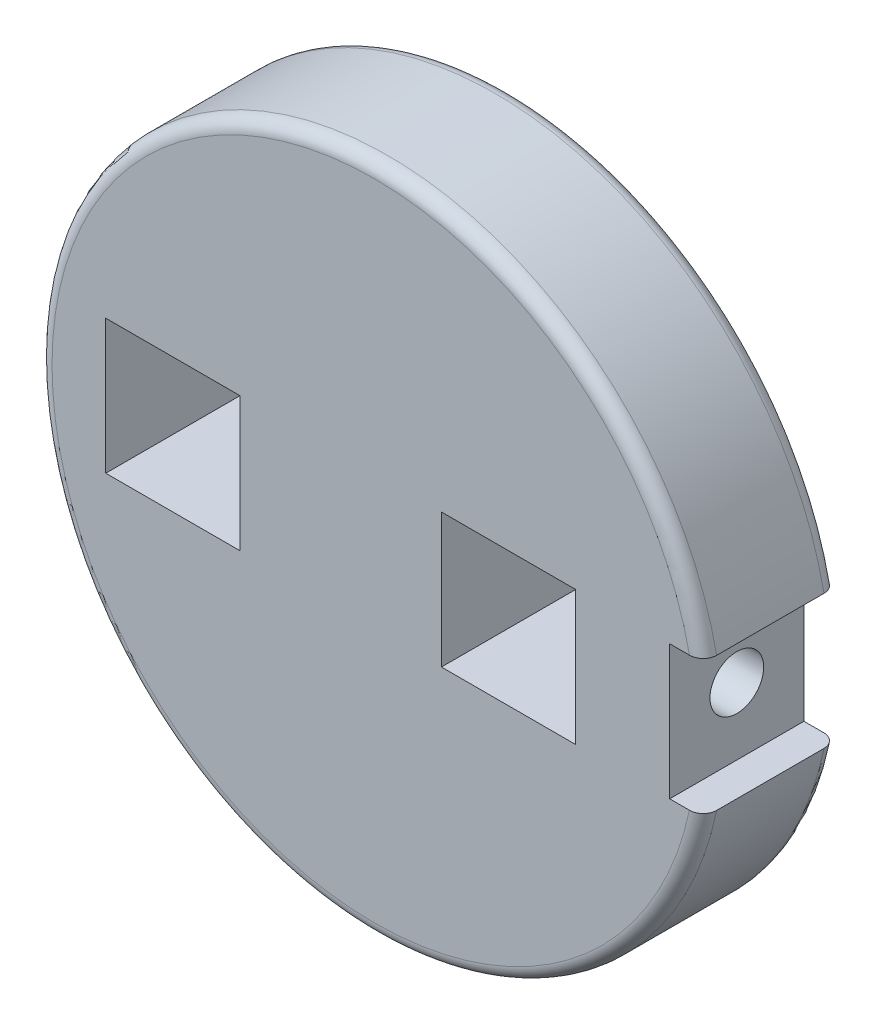
SolidWorks part; units mm, degrees
ref_plane "Front Plane" through (0, 0, 0) normal (0, 0, 1) x (1, 0, 0)
ref_plane "Top Plane" through (0, 0, 0) normal (0, 1, 0) x (1, 0, 0)
ref_plane "Right Plane" through (0, 0, 0) normal (1, 0, 0) x (0, 0, -1)
sketch "Sketch1" plane through (0, 0, 0) normal (0, 0, 1) x (1, 0, 0)
  circle A0 centre (0, 0) radius 25
  dimension "D1" = 50
extrude "Boss-Extrude1" add sketch "Sketch1" along normal blind 10
sketch "Sketch2" plane through (0, 0, 10) normal (0, 0, 1) x (1, 0, 0)
  line L0 (5, -5) -> (15, -5)
  line L1 (-5, -15) -> (5, -15)
  line L2 (-5, -15) -> (-5, -5)
  line L3 (-5, 15) -> (5, 15)
  line L4 (5, -15) -> (5, -5)
  line L5 (-5, -15) -> (5, 15) construction
  line L6 (-5, 15) -> (5, -15) construction
  line L7 (-15, 5) -> (-5, 5)
  line L8 (-15, 5) -> (-15, -5)
  line L9 (-15, -5) -> (-5, -5)
  line L10 (15, 5) -> (15, -5)
  line L11 (-15, 5) -> (15, -5) construction
  line L12 (-15, -5) -> (15, 5) construction
  line L13 (-5, 5) -> (-5, 15)
  line L14 (5, 5) -> (15, 5)
  line L15 (5, 5) -> (5, 15)
  point P0 (0, 0)
  point P5 (0, 0)
  dimension "D1" = 10
  dimension "D2" = 10
  dimension "D3" = 10
  dimension "D4" = 10
extrude "Cut-Extrude1" cut sketch "Sketch2" against normal through all both and the other way through all
sketch "Sketch4" plane through (15, 0, 0) normal (-1, 0, 0) x (0, 0, 1)
  line L0 (0, 5) -> (10, -5) construction
  line L1 (10, -5) -> (10, 5) construction
  line L2 (10, 5) -> (0, -5) construction
  line L4 (4.7591, -4.2656) -> (8.5737, -2.3414)
  line L5 (8.5737, -2.3414) -> (8.8146, 1.9242)
  line L6 (8.8146, 1.9242) -> (5.2409, 4.2656)
  line L7 (5.2409, 4.2656) -> (1.4263, 2.3414)
  line L8 (1.4263, 2.3414) -> (1.1854, -1.9242)
  line L9 (1.1854, -1.9242) -> (4.7591, -4.2656)
  circle A0 centre (5, 0) radius 3.7 construction
extrude "Cut-Extrude2" cut sketch "Sketch4" against normal blind 3
sketch "Sketch5" plane through (18, 0, 0) normal (-1, 0, 0) x (0, 0, 1)
  line L0 (5.2409, 4.2656) -> (4.7591, -4.2656) construction
  circle A0 centre (5, 0) radius 2
  dimension "D1" = 4
extrude "Cut-Extrude4" cut sketch "Sketch5" against normal blind 13 contours A0
fillet "Fillet1" radius 1 2 edges at (25, 0, 0) (25, 0, 10)
sketch3d "3DSketch1"
  spline S0 degree 3 poles (25, -0.2644, 7) (25, 0.1322, 7) (24.999, 0.2622, 6.987) (24.995, 0.5178, 6.9362) (24.992, 0.6449, 6.8977) (24.9846, 0.8871, 6.7973) (24.9802, 1.0019, 6.7359) (24.9705, 1.2193, 6.5907) (24.9652, 1.3221, 6.5063) (24.9495, 1.5988, 6.2296) (24.939, 1.7478, 6.0066) (24.9242, 1.9473, 5.5253) (24.9199, 1.9999, 5.2621) (24.9199, 2.0001, 4.8706) (24.9209, 1.9871, 4.738) (24.9249, 1.936, 4.4815) (24.9279, 1.8983, 4.3568) (24.9353, 1.7981, 4.1146) (24.9398, 1.7355, 3.9975) (24.9494, 1.5908, 3.7809) (24.9546, 1.5082, 3.6798) (24.9652, 1.3216, 3.493) (24.9704, 1.2205, 3.4102) (24.9801, 1.004, 3.2654) (24.9845, 0.8871, 3.2027) (24.992, 0.6449, 3.1023) (24.9949, 0.5202, 3.0644) (24.9989, 0.2639, 3.0132) (25, 0.1313, 3) (25, -0.2604, 2.9999) (24.9957, -0.5236, 3.0522) (24.9809, -1.0051, 3.2514) (24.9705, -1.2283, 3.4002) (24.9548, -1.5051, 3.6765) (24.9495, -1.5896, 3.7793) (24.9398, -1.735, 3.9966) (24.9354, -1.7965, 4.1114) (24.928, -1.8971, 4.3533) (24.925, -1.9357, 4.4804) (24.9209, -1.9868, 4.7361) (24.9199, -1.9999, 4.866) (24.9199, -2.0001, 5.1301) (24.9209, -1.9873, 5.2604) (24.9249, -1.9367, 5.5161) (24.9279, -1.8983, 5.643) (24.9353, -1.7981, 5.8855) (24.9397, -1.7367, 6.0004) (24.9494, -1.5919, 6.2178) (24.9547, -1.5075, 6.3208) (24.9704, -1.231, 6.5977) (24.9808, -1.0081, 6.7469) (24.9956, -0.527, 6.9468) (25, -0.2644, 7) (25, 0.1322, 7) (24.999, 0.2622, 6.987) knots -0.0625 -0.0625 0 0 0.03125 0.03125 0.0625 0.0625 0.09375 0.09375 0.125 0.125 0.1875 0.1875 0.25 0.25 0.28125 0.28125 0.3125 0.3125 0.34375 0.34375 0.375 0.375 0.40625 0.40625 0.4375 0.4375 0.46875 0.46875 0.5 0.5 0.5625 0.5625 0.625 0.625 0.65625 0.65625 0.6875 0.6875 0.71875 0.71875 0.75 0.75 0.78125 0.78125 0.8125 0.8125 0.84375 0.84375 0.875 0.875 0.9375 0.9375 1 1 1.03125 1.03125 1.0625 only from (25, 0, 7) to (25, 0, 7) construction
  point P0 (24.927, 1.9093, 5.5951)
sketch3d "3DSketch2"
  spline S0 degree 3 poles (25, -0.2644, 7) (25, 0.1322, 7) (24.999, 0.2622, 6.987) (24.995, 0.5178, 6.9362) (24.992, 0.6449, 6.8977) (24.9846, 0.8871, 6.7973) (24.9802, 1.0019, 6.7359) (24.9705, 1.2193, 6.5907) (24.9652, 1.3221, 6.5063) (24.9495, 1.5988, 6.2296) (24.939, 1.7478, 6.0066) (24.9242, 1.9473, 5.5253) (24.9199, 1.9999, 5.2621) (24.9199, 2.0001, 4.8706) (24.9209, 1.9871, 4.738) (24.9249, 1.936, 4.4815) (24.9279, 1.8983, 4.3568) (24.9353, 1.7981, 4.1146) (24.9398, 1.7355, 3.9975) (24.9494, 1.5908, 3.7809) (24.9546, 1.5082, 3.6798) (24.9652, 1.3216, 3.493) (24.9704, 1.2205, 3.4102) (24.9801, 1.004, 3.2654) (24.9845, 0.8871, 3.2027) (24.992, 0.6449, 3.1023) (24.9949, 0.5202, 3.0644) (24.9989, 0.2639, 3.0132) (25, 0.1313, 3) (25, -0.2604, 2.9999) (24.9957, -0.5236, 3.0522) (24.9809, -1.0051, 3.2514) (24.9705, -1.2283, 3.4002) (24.9548, -1.5051, 3.6765) (24.9495, -1.5896, 3.7793) (24.9398, -1.735, 3.9966) (24.9354, -1.7965, 4.1114) (24.928, -1.8971, 4.3533) (24.925, -1.9357, 4.4804) (24.9209, -1.9868, 4.7361) (24.9199, -1.9999, 4.866) (24.9199, -2.0001, 5.1301) (24.9209, -1.9873, 5.2604) (24.9249, -1.9367, 5.5161) (24.9279, -1.8983, 5.643) (24.9353, -1.7981, 5.8855) (24.9397, -1.7367, 6.0004) (24.9494, -1.5919, 6.2178) (24.9547, -1.5075, 6.3208) (24.9704, -1.231, 6.5977) (24.9808, -1.0081, 6.7469) (24.9956, -0.527, 6.9468) (25, -0.2644, 7) (25, 0.1322, 7) (24.999, 0.2622, 6.987) knots -0.0625 -0.0625 0 0 0.03125 0.03125 0.0625 0.0625 0.09375 0.09375 0.125 0.125 0.1875 0.1875 0.25 0.25 0.28125 0.28125 0.3125 0.3125 0.34375 0.34375 0.375 0.375 0.40625 0.40625 0.4375 0.4375 0.46875 0.46875 0.5 0.5 0.5625 0.5625 0.625 0.625 0.65625 0.65625 0.6875 0.6875 0.71875 0.71875 0.75 0.75 0.78125 0.78125 0.8125 0.8125 0.84375 0.84375 0.875 0.875 0.9375 0.9375 1 1 1.03125 1.03125 1.0625 only from (25, 0, 7) to (25, 0, 7) construction
  point P0 (24.9992, 0.2052, 3.0106)
ref_plane "Plane2" through (24.9992, 0, 0) normal (1, 0, 0) x (0, 1, 0)
sketch "Sketch6" plane through (24.9992, 0, 0) normal (1, 0, 0) x (0, 1, 0)
  line L0 (0, 5) -> (0, -3.3415) construction
  line L2 (-5, 10) -> (5, 10)
  line L3 (-5, 10) -> (-5, 0)
  line L4 (-5, 0) -> (5, 0)
  line L5 (5, 10) -> (5, 0)
  line L6 (-5, 10) -> (5, 0) construction
  line L7 (-5, 0) -> (5, 10) construction
  dimension "D1" = 10
  dimension "D2" = 10
extrude "Cut-Extrude6" cut sketch "Sketch6" against normal blind 3 and the other way blind 3
sketch "Sketch7" plane through (0, 0, 0) normal (0, 0, -1) x (-1, 0, 0)
  line L1 (-5, 15) -> (5, 15)
  line L2 (-5, 15) -> (-5, -15)
  line L3 (-5, -15) -> (5, -15)
  line L4 (5, 15) -> (5, -15)
extrude "Boss-Extrude2" add sketch "Sketch7" against normal blind 10
sketch "Sketch8" plane through (0, 0, 0) normal (0, 0, -1) x (-1, 0, 0)
  line L1 (5, 5) -> (15, 5)
  line L2 (5, 5) -> (5, -5)
  line L3 (5, -5) -> (15, -5)
  line L4 (15, 5) -> (15, -5)
extrude "Boss-Extrude3" add sketch "Sketch8" against normal blind 10
sketch "Sketch9" plane through (0, 0, 0) normal (0, 0, -1) x (-1, 0, 0)
  line L0 (0, 0) -> (0, 15) construction
  line L1 (0, 0) -> (15, 0) construction
  line L3 (20, 5) -> (10, 5)
  line L4 (20, 5) -> (20, -5)
  line L5 (20, -5) -> (10, -5)
  line L6 (10, 5) -> (10, -5)
  line L7 (20, 5) -> (10, -5) construction
  line L8 (20, -5) -> (10, 5) construction
  dimension "D1" = 15
  dimension "D2" = 15
  dimension "D3" = 10
extrude "Cut-Extrude7" cut sketch "Sketch9" against normal blind 10 contours L4 L3 L6 L5
